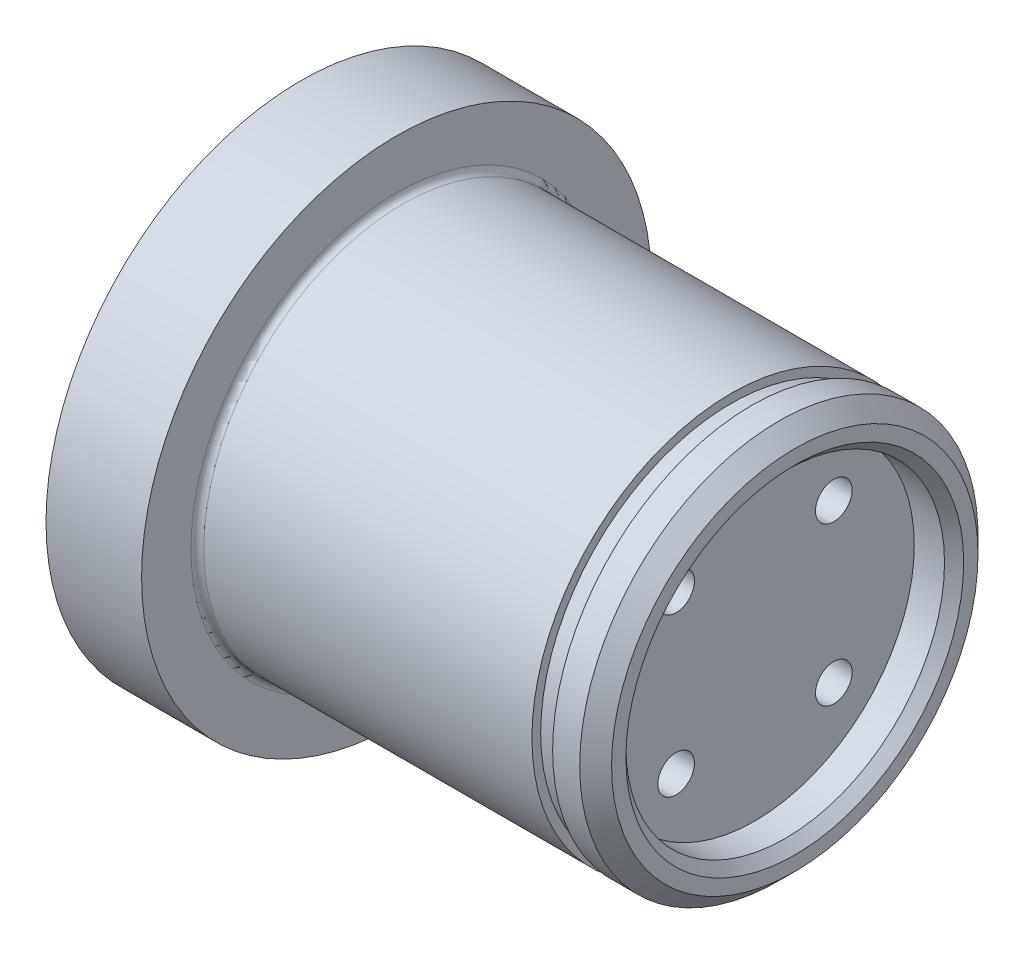
SolidWorks part; units mm, degrees
material "1060 Сплав"
ref_plane "Спереди" through (0, 0, 0) normal (0, 0, 1) x (1, 0, 0)
ref_plane "Сверху" through (0, 0, 0) normal (0, 1, 0) x (1, 0, 0)
ref_plane "Справа" through (0, 0, 0) normal (1, 0, 0) x (0, 0, -1)
sketch "Эскиз1" plane through (0, 0, 0) normal (0, 0, 1) x (1, 0, 0)
  line L0 (0, 0) -> (22138.4448, 0) construction
  line L1 (0, 0) -> (0, 12.5)
  line L2 (0, 12.5) -> (-25, 12.5)
  line L3 (-25, 12.5) -> (-25, 16)
  line L4 (-25, 16) -> (-31, 16)
  line L5 (-31, 16) -> (-31, 0)
  line L8 (0, 0) -> (-31, 0)
  dimension "D1" = 31
  dimension "D2" = 6
  dimension "D3" = 25
  dimension "D6" = 32
revolve "Повернуть1" add sketch "Эскиз1" angle 360 about L0
sketch "Эскиз2" plane through (0, 0, 0) normal (0, 0, 1) x (1, 0, 0)
  line L0 (-4, 12.5) -> (-4, 11.95)
  line L1 (0, 12.5) -> (-25, 12.5) construction
  line L2 (-4, 11.95) -> (-2.7, 11.95)
  line L3 (-2.7, 11.95) -> (-2.7, 12.5)
  line L4 (-2.7, 12.5) -> (-4, 12.5)
  line L5 (0, -12.5) -> (0, 12.5) construction
  line L6 (0, 0) -> (-50000, 0) construction
  point P10 (-2.7, 12.225)
  point P13 (0, 0)
  dimension "D1" = 4
  dimension "D2" = 1.3
  dimension "D3" = 23.9
revolve "Вырез-Повернуть1" cut sketch "Эскиз2" angle 360 about L6
chamfer "Фаска1" distance 1 angle 45 1 edges at (0, 0, 12.5)
fillet "Скругление1" radius 0.4 1 edges at (-25, 0, 12.5)
hole_wizard "Сверло под метчик  спиральное M2.21" positions "Эскиз3" profile "Эскиз4" hole size "M2.2x0.45" standard "Ansi Metric"
sketch "Эскиз3" plane through (0, 0, 0) normal (1, 0, 0) x (0, 0, -1)
  line L0 (0, 0) -> (0, 7) construction
  line L2 (0, 0) -> (4.9497, 4.9497) construction
  circle A0 centre (0, 0) radius 7 construction
  point P0 (4.9497, 4.9497)
  dimension "D1" = 14
  dimension "D2" = 45
sketch "Эскиз4" plane through (0, 4.9497, -4.9497) normal (0, 1, 0) x (0, 0, -1)
  line L0 (0, 0) -> (0, 10.691)
  line L1 (0, 10.691) -> (1.15, 10)
  line L2 (1.15, 10) -> (1.15, 0)
  line L5 (1.15, 0) -> (0, 0)
  line L10 (0, 10.691) -> (-1.15, 10) construction
  line L11 (0, -6.35) -> (0, 107.95) construction
  dimension "Диаметр отверстия" = 2.3
  dimension "Глубина отверстия" = 10
  dimension "Угол заточки сверла" = 118
pattern_circular "Круговой массив1" count 4 over 360 about axis through (0, 0, 0) along (-1, 0, 0) of "Сверло под метчик  спиральное M2.21"
sketch "Эскиз5" plane through (0, 0, 0) normal (0, 0, 1) x (1, 0, 0)
  line L0 (0, 0) -> (0, 10)
  line L1 (0, -11.5) -> (0, 11.5) construction
  line L7 (0, 10) -> (-2.5, 10)
  line L8 (-2.5, 10) -> (-2.5, 0)
  line L9 (-2.5, 0) -> (0, 0)
  line L10 (0, 0) -> (-50000, 0) construction
  dimension "D1" = 2.5
  dimension "D2" = 20
revolve "Вырез-Повернуть2" cut sketch "Эскиз5" angle 360 about L10
chamfer "Фаска2" distance 0.6 angle 45 1 edges at (0, 0, -10)
hole_wizard "Сверло под метчик  спиральное M2.22" positions "Эскиз6" profile "Эскиз7" hole size "M2.2x0.45" standard "Ansi Metric"
sketch "Эскиз6" plane through (-31, 0, 0) normal (-1, 0, 0) x (0, 0, 1)
  point P2 (0, 10)
  point P5 (0, 0)
  point P7 (0, 0)
  dimension "D1" = 10
sketch "Эскиз7" plane through (-31, 10, 0) normal (0, 1, 0) x (0, 0, 1)
  line L0 (0, 0) -> (0, 10.691)
  line L1 (0, 10.691) -> (1.15, 10)
  line L2 (1.15, 10) -> (1.15, 0)
  line L5 (1.15, 0) -> (0, 0)
  line L10 (0, 10.691) -> (-1.15, 10) construction
  line L11 (0, -6.35) -> (0, 107.95) construction
  dimension "Диаметр отверстия" = 2.3
  dimension "Глубина отверстия" = 10
  dimension "Угол заточки сверла" = 118
pattern_circular "Круговой массив2" count 4 over 360 about axis through (-31, 0, 0) along (-1, 0, 0) of "Сверло под метчик  спиральное M2.22"
